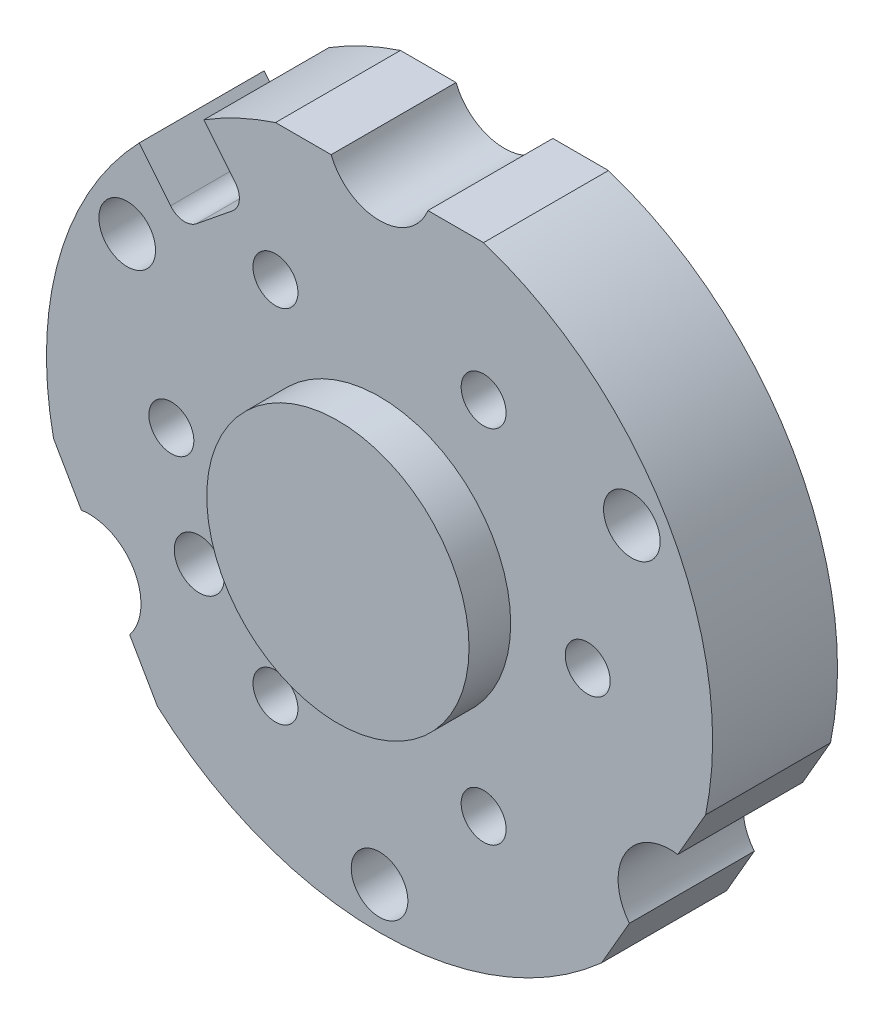
SolidWorks part; units mm, degrees
material "Lega 1060"
ref_plane "Piano frontale" through (0, 0, 0) normal (0, 0, 1) x (1, 0, 0)
ref_plane "Piano superiore" through (0, 0, 0) normal (0, 1, 0) x (1, 0, 0)
ref_plane "Piano destro" through (0, 0, 0) normal (1, 0, 0) x (0, 0, -1)
sketch "Schizzo1" plane through (0, 0, 0) normal (0, 0, 1) x (1, 0, 0)
  line L9 (-5.8114, 38) -> (-12.49, 38)
  line L10 (-21.0896, 33.9886) -> (-17.3224, 29.3364)
  line L11 (-17.6476, 26.2422) -> (-21.9996, 22.718)
  line L12 (-25.0938, 23.0432) -> (-28.8611, 27.6954)
  line L13 (-39.154, -8.1833) -> (-35.8146, -13.9673)
  line L14 (-30.0029, -24.0334) -> (-26.664, -29.8167)
  line L15 (26.664, -29.8167) -> (30.0029, -24.0334)
  line L16 (35.8146, -13.9673) -> (39.154, -8.1833)
  line L17 (12.49, 38) -> (5.8114, 38)
  line L18 (-5.8114, 38) -> (-12.49, 38)
  line L19 (-21.0896, 33.9886) -> (-17.3224, 29.3364)
  line L20 (-17.6476, 26.2422) -> (-21.9996, 22.718)
  line L21 (-25.0938, 23.0432) -> (-28.8611, 27.6954)
  line L22 (-39.154, -8.1833) -> (-35.8146, -13.9673)
  line L23 (-30.0029, -24.0334) -> (-26.664, -29.8167)
  line L24 (26.664, -29.8167) -> (30.0029, -24.0334)
  line L25 (35.8146, -13.9673) -> (39.154, -8.1833)
  line L26 (12.49, 38) -> (5.8114, 38)
  arc A9 (-12.49, 38) -> (-21.0896, 33.9886) centre (0, 0) ccw
  arc A10 (-17.6476, 26.2422) -> (-17.3224, 29.3364) centre (-19.0321, 27.9519) ccw
  arc A11 (-25.0938, 23.0432) -> (-21.9996, 22.718) centre (-23.3841, 24.4277) ccw
  arc A12 (-28.8611, 27.6954) -> (-39.154, -8.1833) centre (0, 0) ccw
  arc A13 (-30.0029, -24.0334) -> (-35.8146, -13.9673) centre (-34.9, -20.15) ccw
  arc A14 (-26.664, -29.8167) -> (26.664, -29.8167) centre (0, 0) ccw
  arc A15 (35.8146, -13.9673) -> (30.0029, -24.0334) centre (34.9, -20.15) ccw
  arc A16 (39.154, -8.1833) -> (12.49, 38) centre (0, 0) ccw
  arc A17 (-5.8114, 38) -> (5.8114, 38) centre (0, 40.3) ccw
  arc A18 (-12.49, 38) -> (-21.0896, 33.9886) centre (0, 0) ccw
  arc A19 (-17.6476, 26.2422) -> (-17.3224, 29.3364) centre (-19.0321, 27.9519) ccw
  arc A20 (-25.0938, 23.0432) -> (-21.9996, 22.718) centre (-23.3841, 24.4277) ccw
  arc A21 (-28.8611, 27.6954) -> (-39.154, -8.1833) centre (0, 0) ccw
  arc A22 (-30.0029, -24.0334) -> (-35.8146, -13.9673) centre (-34.9, -20.15) ccw
  arc A23 (-26.664, -29.8167) -> (26.664, -29.8167) centre (0, 0) ccw
  arc A24 (35.8146, -13.9673) -> (30.0029, -24.0334) centre (34.9, -20.15) ccw
  arc A25 (39.154, -8.1833) -> (12.49, 38) centre (0, 0) ccw
  arc A26 (-5.8114, 38) -> (5.8114, 38) centre (0, 40.3) ccw
  dimension "D1" = 0
extrude "Estrusione-Estrusione1" add sketch "Schizzo1" along normal up to surface (15 mm away)
sketch "Schizzo5" plane through (0, 0, 0) normal (0, 0, -1) x (-1, 0, 0)
  arc A0 (0, -27.5) -> (0, 27.5) centre (0, 0) ccw construction
  arc A1 (0, 27.5) -> (0, -27.5) centre (0, 0) ccw construction
  arc A2 (0, -27.5) -> (0, 27.5) centre (0, 0) ccw
  arc A3 (0, 27.5) -> (0, -27.5) centre (0, 0) ccw
extrude "Estrusione-Estrusione5" add sketch "Schizzo5" along normal blind 0.3 contours A3 A2
sketch "Schizzo2" plane through (0, 0, 15) normal (0, 0, 1) x (1, 0, 0)
  arc A0 (26.25, -2.1651) -> (23.75, 2.1651) centre (25, 0) ccw construction
  arc A1 (23.75, 2.1651) -> (26.25, -2.1651) centre (25, 0) ccw construction
  arc A2 (11.25, 23.8157) -> (13.75, 19.4856) centre (12.5, 21.6506) ccw construction
  arc A3 (13.75, 19.4856) -> (11.25, 23.8157) centre (12.5, 21.6506) ccw construction
  arc A4 (-23.75, -2.1651) -> (-26.25, 2.1651) centre (-25, 0) ccw construction
  arc A5 (-26.25, 2.1651) -> (-23.75, -2.1651) centre (-25, 0) ccw construction
  arc A6 (-23.1506, -9.9019) -> (-20.1506, -15.0981) centre (-21.6506, -12.5) ccw construction
  arc A7 (-20.1506, -15.0981) -> (-23.1506, -9.9019) centre (-21.6506, -12.5) ccw construction
  arc A8 (-13.75, 23.8157) -> (-11.25, 19.4856) centre (-12.5, 21.6506) ccw construction
  arc A9 (-11.25, 19.4856) -> (-13.75, 23.8157) centre (-12.5, 21.6506) ccw construction
  arc A10 (11.25, -19.4856) -> (13.75, -23.8157) centre (12.5, -21.6506) ccw construction
  arc A11 (-13.75, -19.4856) -> (-11.25, -23.8157) centre (-12.5, -21.6506) ccw construction
  arc A12 (-11.25, -23.8157) -> (-13.75, -19.4856) centre (-12.5, -21.6506) ccw construction
  arc A13 (13.75, -23.8157) -> (11.25, -19.4856) centre (12.5, -21.6506) ccw construction
  arc A14 (26.25, -2.1651) -> (23.75, 2.1651) centre (25, 0) ccw
  arc A15 (23.75, 2.1651) -> (26.25, -2.1651) centre (25, 0) ccw
  arc A16 (11.25, 23.8157) -> (13.75, 19.4856) centre (12.5, 21.6506) ccw
  arc A17 (13.75, 19.4856) -> (11.25, 23.8157) centre (12.5, 21.6506) ccw
  arc A18 (-23.75, -2.1651) -> (-26.25, 2.1651) centre (-25, 0) ccw
  arc A19 (-26.25, 2.1651) -> (-23.75, -2.1651) centre (-25, 0) ccw
  arc A20 (-23.1506, -9.9019) -> (-20.1506, -15.0981) centre (-21.6506, -12.5) ccw
  arc A21 (-20.1506, -15.0981) -> (-23.1506, -9.9019) centre (-21.6506, -12.5) ccw
  arc A22 (-13.75, 23.8157) -> (-11.25, 19.4856) centre (-12.5, 21.6506) ccw
  arc A23 (-11.25, 19.4856) -> (-13.75, 23.8157) centre (-12.5, 21.6506) ccw
  arc A24 (11.25, -19.4856) -> (13.75, -23.8157) centre (12.5, -21.6506) ccw
  arc A25 (-13.75, -19.4856) -> (-11.25, -23.8157) centre (-12.5, -21.6506) ccw
  arc A26 (-11.25, -23.8157) -> (-13.75, -19.4856) centre (-12.5, -21.6506) ccw
  arc A27 (13.75, -23.8157) -> (11.25, -19.4856) centre (12.5, -21.6506) ccw
  arc A28 (-11.15, 19.3124) -> (-13.85, 23.9889) centre (-12.5, 21.6506) ccw
  arc A29 (-13.85, 23.9889) -> (-11.15, 19.3124) centre (-12.5, 21.6506) ccw
  arc A30 (11.15, 23.9889) -> (13.85, 19.3124) centre (12.5, 21.6506) ccw
  arc A31 (13.85, 19.3124) -> (11.15, 23.9889) centre (12.5, 21.6506) ccw
  arc A32 (26.35, -2.3383) -> (23.65, 2.3383) centre (25, 0) ccw
  arc A33 (23.65, 2.3383) -> (26.35, -2.3383) centre (25, 0) ccw
  arc A34 (13.85, -23.9889) -> (11.15, -19.3124) centre (12.5, -21.6506) ccw
  arc A35 (11.15, -19.3124) -> (13.85, -23.9889) centre (12.5, -21.6506) ccw
  arc A36 (-11.15, -23.9889) -> (-13.85, -19.3124) centre (-12.5, -21.6506) ccw
  arc A37 (-13.85, -19.3124) -> (-11.15, -23.9889) centre (-12.5, -21.6506) ccw
  arc A38 (-23.65, -2.3383) -> (-26.35, 2.3383) centre (-25, 0) ccw
  arc A39 (-26.35, 2.3383) -> (-23.65, -2.3383) centre (-25, 0) ccw
  dimension "D1" = 0.2
extrude "Taglio-Estrusione1" cut sketch "Schizzo2" against normal through all contours A31 A30 | A29 A28 | A38 A39 | A21 A20 | A36 A37 | A34 A35 | A32 A33
sketch "Schizzo3" plane through (0, 0, 0) normal (0, 0, -1) x (-1, 0, 0)
  arc A0 (30.3, 20.9) -> (30.3, 14.1) centre (30.3, 17.5) ccw construction
  arc A1 (30.3, 14.1) -> (30.3, 20.9) centre (30.3, 17.5) ccw construction
  arc A2 (0, -38.4) -> (0, -31.6) centre (0, -35) ccw construction
  arc A3 (0, -31.6) -> (0, -38.4) centre (0, -35) ccw construction
  arc A4 (-30.3, 20.9) -> (-30.3, 14.1) centre (-30.3, 17.5) ccw construction
  arc A5 (-30.3, 14.1) -> (-30.3, 20.9) centre (-30.3, 17.5) ccw construction
  arc A6 (30.3, 20.9) -> (30.3, 14.1) centre (30.3, 17.5) ccw
  arc A7 (30.3, 14.1) -> (30.3, 20.9) centre (30.3, 17.5) ccw
  arc A8 (0, -38.4) -> (0, -31.6) centre (0, -35) ccw
  arc A9 (0, -31.6) -> (0, -38.4) centre (0, -35) ccw
  arc A10 (-30.3, 20.9) -> (-30.3, 14.1) centre (-30.3, 17.5) ccw
  arc A11 (-30.3, 14.1) -> (-30.3, 20.9) centre (-30.3, 17.5) ccw
extrude "Taglio-Estrusione2" cut sketch "Schizzo3" against normal through all
sketch "Schizzo4" plane through (0, 0, 15) normal (0, 0, 1) x (1, 0, 0)
  arc A0 (-7.875, 13.6399) -> (7.875, -13.6399) centre (0, 0) ccw construction
  arc A1 (7.875, -13.6399) -> (-7.875, 13.6399) centre (0, 0) ccw construction
  arc A2 (-7.875, 13.6399) -> (7.875, -13.6399) centre (0, 0) ccw
  arc A3 (7.875, -13.6399) -> (-7.875, 13.6399) centre (0, 0) ccw
extrude "Estrusione-Estrusione2" add sketch "Schizzo4" along normal blind 5
sketch "Schizzo7" plane through (0, 0, -0.3) normal (0, 0, -1) x (-1, 0, 0)
  circle A0 centre (-12.5, 21.6506) radius 6
  circle A1 centre (12.5, 21.6506) radius 6
  circle A2 centre (25, 0) radius 6
  circle A4 centre (12.5, -21.6506) radius 6
  circle A5 centre (-12.5, -21.6506) radius 6
  circle A6 centre (-25, 0) radius 6
  dimension "D1" = 12
extrude "Taglio-Estrusione3" cut sketch "Schizzo7" against normal blind 7
sketch "Schizzo8" plane through (0, 0, 15) normal (0, 0, 1) x (1, 0, 0)
  point P0 (0, 0)
